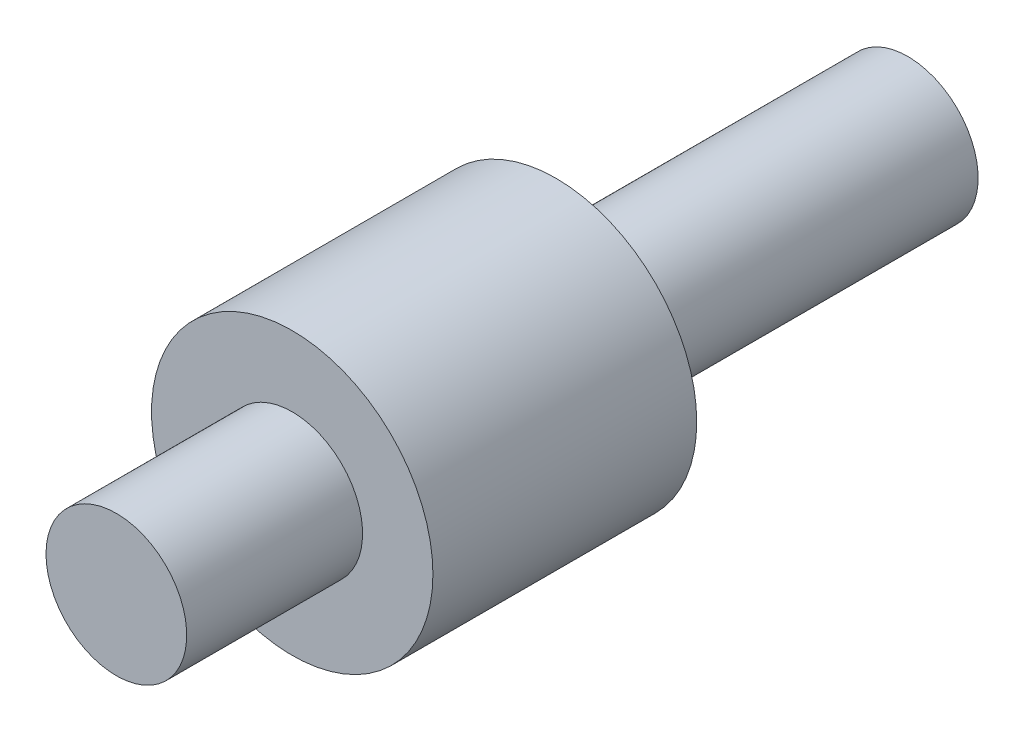
SolidWorks part; units mm, degrees
ref_plane "Front Plane" through (0, 0, 0) normal (0, 0, 1) x (1, 0, 0)
ref_plane "Top Plane" through (0, 0, 0) normal (0, 1, 0) x (1, 0, 0)
ref_plane "Right Plane" through (0, 0, 0) normal (1, 0, 0) x (0, 0, -1)
sketch "Sketch1" plane through (0, 0, 0) normal (0, 0, 1) x (1, 0, 0)
  circle A0 centre (0, 0) radius 2
  dimension "D1" = 4
extrude "Boss-Extrude1" add sketch "Sketch1" along normal blind 22.5
ref_plane "Plane1" through (0, 0, 10) normal (0, 0, -1) x (-1, 0, 0)
ref_plane "Plane2" through (0, 0, 17.5) normal (0, 0, 1) x (1, 0, 0)
sketch "Sketch3" plane through (0, 0, 17.5) normal (0, 0, 1) x (1, 0, 0)
  circle A0 centre (0, 0) radius 4
  dimension "D1" = 8
extrude "Boss-Extrude3" add sketch "Sketch3" against normal up to surface (7.5 mm away) up to plane "Plane1"
